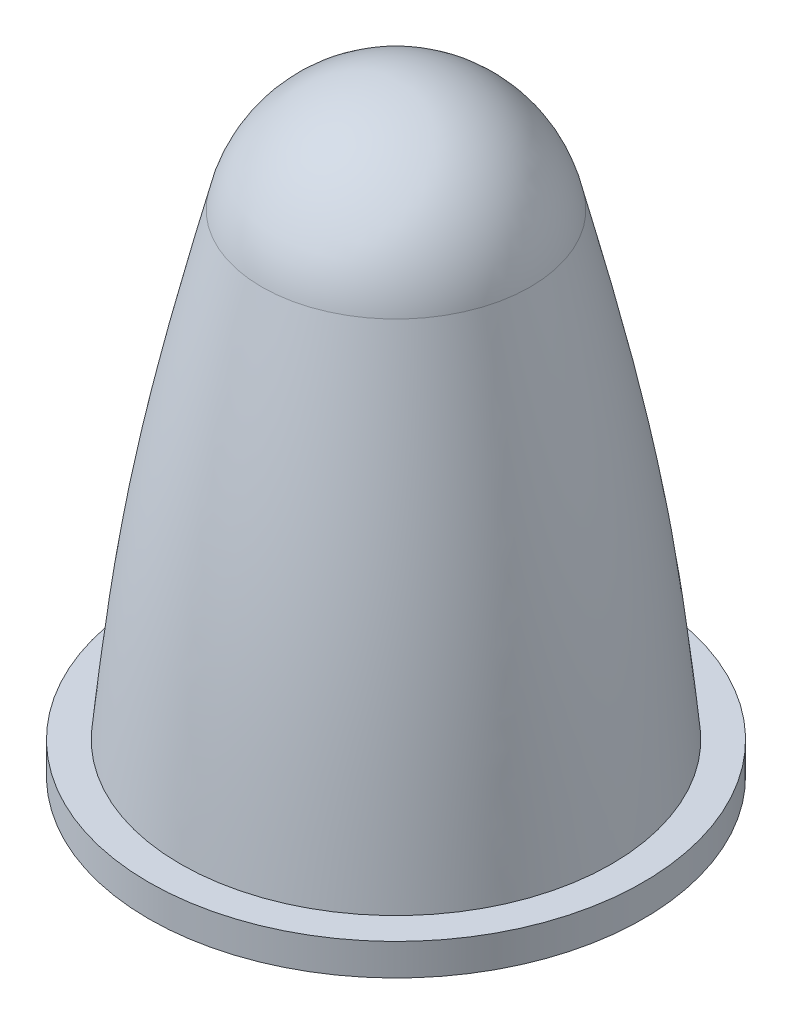
SolidWorks part; units mm, degrees
ref_plane "Front Plane" through (0, 0, 0) normal (0, 0, 1) x (1, 0, 0)
ref_plane "Top Plane" through (0, 0, 0) normal (0, 1, 0) x (1, 0, 0)
ref_plane "Right Plane" through (0, 0, 0) normal (1, 0, 0) x (0, 0, -1)
sketch "Sketch1" plane through (0, 0, 0) normal (0, 0, 1) x (1, 0, 0)
  line L0 (0, 0) -> (-6.8059, 0)
  line L4 (0, 18) -> (0, 0)
  arc A0 (-4.2417, 14.5) -> (0, 18) centre (0, 13.6797) cw
  spline S0 degree 3 poles (-6.8059, 0) (-6.3105, 4.9997) (-5.9317, 7.7853) (-4.2417, 14.5) knots 0 0 0 0 1 1 1 1
  point P3 (0, 12.8384)
  point P4 (-6.8059, 0)
  point P8 (-4.2417, 14.5)
  dimension "D1" = 3.5
  dimension "D2" = 18
revolve "Revolve1" add sketch "Sketch1" angle 360 about L4
sketch "Sketch3" plane through (0, 0, 0) normal (0, -1, 0) x (1, 0, 0)
  circle A0 centre (0, 0) radius 7.8059
  circle A2 centre (0, 0) radius 6.8059 construction
  dimension "D1" = 1
extrude "Boss-Extrude1" add sketch "Sketch3" along normal blind 1
sketch "Sketch5" plane through (0, -1, 0) normal (0, -1, 0) x (1, 0, 0)
  circle A0 centre (0, 0) radius 3
  dimension "D1" = 6
extrude "Cut-Extrude1" cut sketch "Sketch5" against normal blind 10
